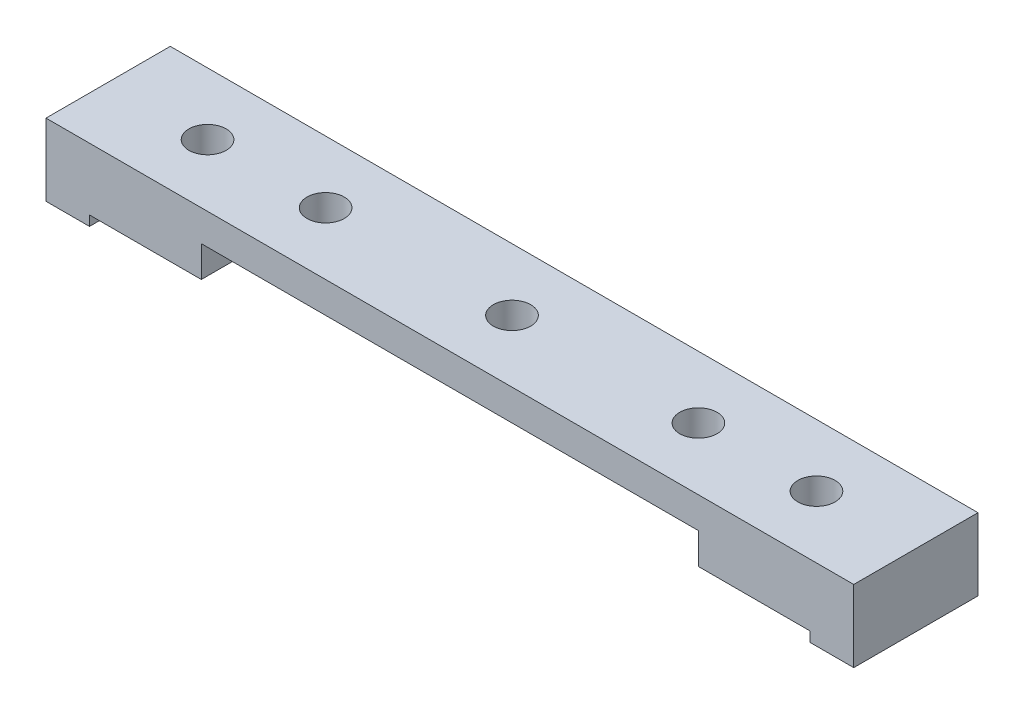
SolidWorks part; units mm, degrees
ref_plane "Front Plane" through (0, 0, 0) normal (0, 0, 1) x (1, 0, 0)
ref_plane "Top Plane" through (0, 0, 0) normal (0, 1, 0) x (1, 0, 0)
ref_plane "Right Plane" through (0, 0, 0) normal (1, 0, 0) x (0, 0, -1)
sketch "Sketch1" plane through (0, 0, 0) normal (0, 1, 0) x (1, 0, 0)
  line L0 (32.5, 5) -> (32.5, 10) construction
  line L1 (0, 0) -> (65, 0)
  line L2 (0, 0) -> (0, 10)
  line L3 (0, 10) -> (65, 10)
  line L4 (65, 0) -> (65, 10)
  circle A0 centre (17.5, 5) radius 1.5
  circle A1 centre (32.5, 5) radius 1.5
  circle A2 centre (47.5, 5) radius 1.5
  circle A3 centre (8, 5) radius 1.5
  circle A4 centre (57, 5) radius 1.5
  dimension "D3" = 3
  dimension "D1" = 10
  dimension "D2" = 65
  dimension "D4" = 5
  dimension "D5" = 15
  dimension "D6" = 15
  dimension "D7" = 9.5
  dimension "D8" = 9.5
extrude "Boss-Extrude1" add sketch "Sketch1" along normal blind 5
sketch "Sketch2" plane through (0, 0, 0) normal (0, -1, 0) x (1, 0, 0)
  line L0 (0, 0) -> (65, 0) construction
  line L1 (12.5, 0) -> (52.5, 0)
  line L2 (12.5, 0) -> (12.5, -10)
  line L3 (12.5, -10) -> (52.5, -10)
  line L4 (52.5, 0) -> (52.5, -10)
  line L5 (65, -10) -> (0, -10) construction
  circle A0 centre (17.5, -5) radius 1.5 construction
  dimension "D1" = 40
  dimension "D2" = 5
extrude "Cut-Extrude1" cut sketch "Sketch2" against normal offset from surface (2.5 mm away) 2.5 up to face at (8, 5, -3.5)
sketch "Sketch3" plane through (0, 0, 0) normal (0, -1, 0) x (1, 0, 0)
  line L0 (12.5, -10) -> (0, -10) construction
  line L1 (0, 0) -> (3.5, 0)
  line L2 (0, 0) -> (0, -10)
  line L3 (0, -10) -> (3.5, -10)
  line L4 (3.5, 0) -> (3.5, -10)
  line L5 (65, -10) -> (52.5, -10) construction
  line L6 (65, 0) -> (61.5, 0)
  line L7 (65, 0) -> (65, -10)
  line L8 (65, -10) -> (61.5, -10)
  line L9 (61.5, 0) -> (61.5, -10)
  dimension "D1" = 3.5
extrude "Boss-Extrude2" add sketch "Sketch3" along normal blind 0.8
